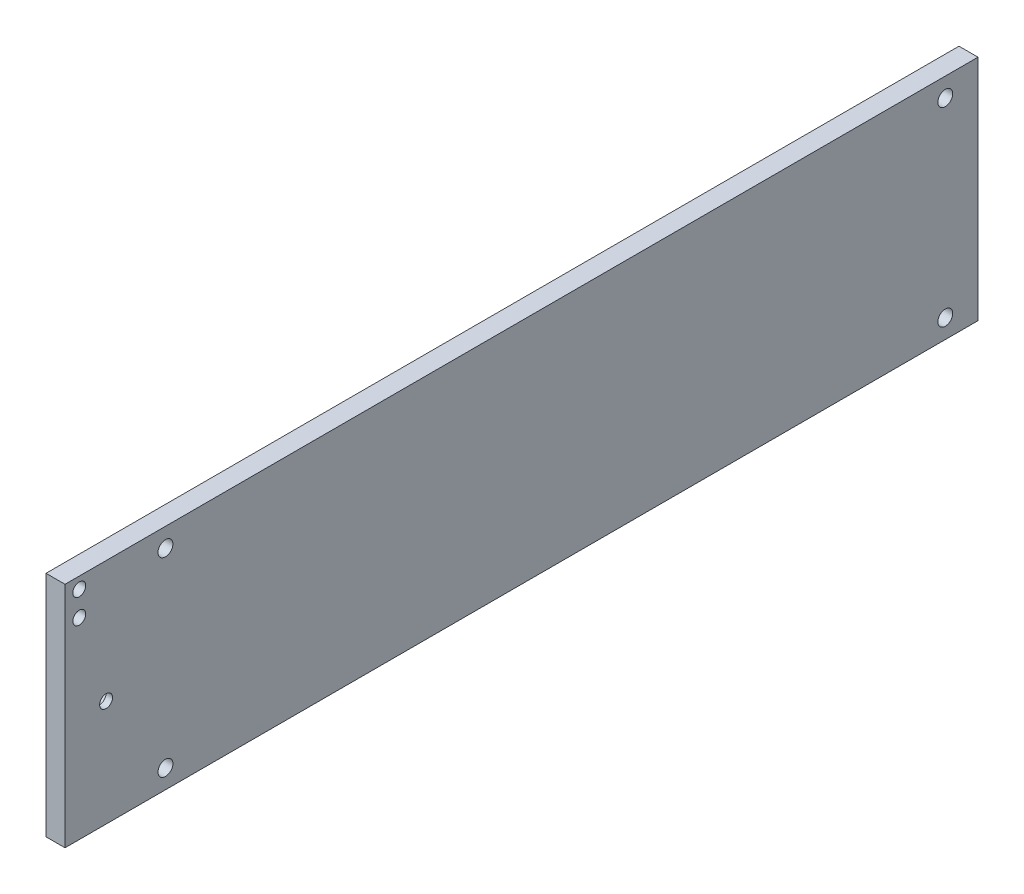
SolidWorks part; units mm, degrees
material "6061-T6 (SS)"
ref_plane "Front Plane" through (0, 0, 0) normal (0, 0, 1) x (1, 0, 0)
ref_plane "Top Plane" through (0, 0, 0) normal (0, 1, 0) x (1, 0, 0)
ref_plane "Right Plane" through (0, 0, 0) normal (1, 0, 0) x (0, 0, -1)
sketch "Sketch1" plane through (0, 0, 0) normal (1, 0, 0) x (0, 0, -1)
  line L1 (-152.4, 38.1) -> (152.4, 38.1)
  line L2 (-152.4, 38.1) -> (-152.4, -38.1)
  line L3 (-152.4, -38.1) -> (152.4, -38.1)
  line L4 (152.4, 38.1) -> (152.4, -38.1)
  line L5 (-152.4, 38.1) -> (152.4, -38.1) construction
  line L6 (-152.4, -38.1) -> (152.4, 38.1) construction
  point P0 (0, 0)
  dimension "D1" = 76.2
  dimension "D2" = 304.8
extrude "Boss-Extrude1" add sketch "Sketch1" along normal blind 6.35
sketch "Sketch2" plane through (6.35, 0, 0) normal (1, 0, 0) x (0, 0, -1)
  line L0 (152.4, -38.1) -> (152.4, 38.1) construction
  line L1 (-118.872, 31.75) -> (141.478, 31.75) construction
  line L2 (-118.872, 31.75) -> (-118.872, -31.75) construction
  line L3 (-118.872, -31.75) -> (141.478, -31.75) construction
  line L4 (141.478, 31.75) -> (141.478, -31.75) construction
  line L5 (-118.872, 31.75) -> (141.478, -31.75) construction
  line L6 (-118.872, -31.75) -> (141.478, 31.75) construction
  line L7 (-152.4, 38.1) -> (-152.4, -38.1) construction
  line L8 (-152.4, -38.1) -> (152.4, -38.1) construction
  point P0 (11.303, 0)
  point P7 (0, 0)
  point P8 (-138.684, -2.54)
  dimension "D1" = 10.922
  dimension "D2" = 33.528
  dimension "D3" = 63.5
  dimension "D4" = 13.716
  dimension "D5" = 35.56
hole_wizard "#10 Clearance Hole1" positions "Sketch3" profile "Sketch4" hole size "#10" standard "ANSI Inch" end condition through all
sketch "Sketch3" plane through (6.35, 0, 0) normal (1, 0, 0) x (0, 0, -1)
  point P0 (-118.872, 31.75)
  point P3 (-118.872, -31.75)
  point P6 (141.478, -31.75)
  point P9 (141.478, 31.75)
sketch "Sketch4" plane through (6.35, 31.75, 118.872) normal (0, 1, 0) x (0, 0, -1)
  line L0 (0, 0) -> (0, 6.35)
  line L1 (0, 6.35) -> (2.4892, 6.35)
  line L2 (2.4892, 6.35) -> (2.4892, 0)
  line L5 (2.4892, 0) -> (0, 0)
  line L11 (0, -6.35) -> (0, 107.95) construction
  dimension "Thru Hole Dia." = 4.9784
  dimension "Thru Hole Depth" = 6.35
hole_wizard "CBORE for #8 Socket Head Cap Screw2" positions "Sketch8" profile "Sketch9" counterbore size "#8" standard "ANSI Inch"
sketch "Sketch8" plane through (0, 0, 0) normal (-1, 0, 0) x (0, 0, 1)
  point P0 (138.684, -2.54)
sketch "Sketch9" plane through (0, -2.54, 138.684) normal (0, 1, 0) x (0, 0, 1)
  line L0 (0, 0) -> (0, 11.9614)
  line L1 (0, 11.9614) -> (2.1526, 10.668)
  line L2 (2.1526, 10.668) -> (2.1526, 4.1656)
  line L3 (2.1526, 4.1656) -> (3.9687, 4.1656)
  line L4 (3.9687, 4.1656) -> (3.9687, 0)
  line L5 (3.9687, 0) -> (0, 0)
  line L10 (0, 11.9614) -> (-2.1527, 10.668) construction
  line L11 (0, -6.35) -> (0, 107.95) construction
  dimension "Hole Dia." = 4.3053
  dimension "Hole Depth" = 10.668
  dimension "C'Bore Dia." = 7.9375
  dimension "C'Bore Depth" = 4.1656
  dimension "Drill Angle" = 118
sketch "Sketch10" plane through (0, 0, 0) normal (-1, 0, 0) x (0, 0, 1)
  line L0 (147.6375, 34.2519) -> (147.6375, 26.0731) construction
  line L1 (152.4, 38.1) -> (152.4, -38.1) construction
  line L2 (-152.4, 38.1) -> (152.4, 38.1) construction
  point P2 (147.6375, 30.1625)
  dimension "D1" = 4.7625
  dimension "D2" = 7.9375
  dimension "D3" = 8.1788
hole_wizard "#8 Clearance Hole1" positions "Sketch11" profile "Sketch12" hole size "#8" standard "ANSI Inch" end condition through all
sketch "Sketch11" plane through (0, 0, 0) normal (-1, 0, 0) x (0, 0, 1)
  point P0 (147.6375, 34.2519)
  point P3 (147.6375, 26.0731)
sketch "Sketch12" plane through (0, 34.2519, 147.6375) normal (0, 1, 0) x (0, 0, 1)
  line L0 (0, 0) -> (0, 6.35)
  line L1 (0, 6.35) -> (2.1526, 6.35)
  line L2 (2.1526, 6.35) -> (2.1526, 0)
  line L5 (2.1526, 0) -> (0, 0)
  line L11 (0, -6.35) -> (0, 107.95) construction
  dimension "Thru Hole Dia." = 4.3053
  dimension "Thru Hole Depth" = 6.35
